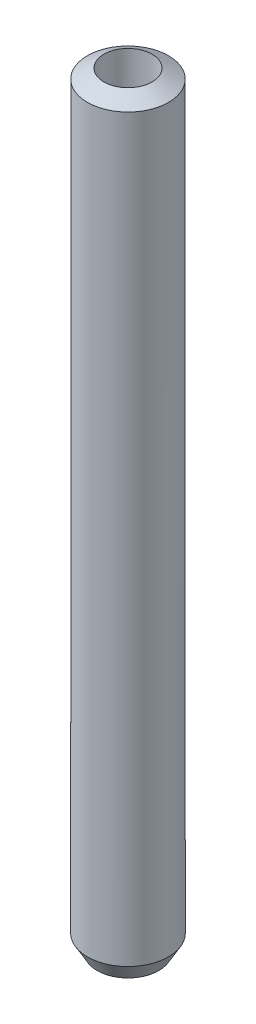
SolidWorks part; units mm, degrees
ref_plane "Front Plane" through (0, 0, 0) normal (0, 0, 1) x (1, 0, 0)
ref_plane "Top Plane" through (0, 0, 0) normal (0, 1, 0) x (1, 0, 0)
ref_plane "Right Plane" through (0, 0, 0) normal (1, 0, 0) x (0, 0, -1)
sketch "Sketch1" plane through (0, 0, 0) normal (0, 1, 0) x (1, 0, 0)
  circle A0 centre (0, 0) radius 7.5
  dimension "SHAFT_OD" = 15
extrude "Boss-Extrude1" add sketch "Sketch1" along normal blind 141.8844
sketch "Sketch2" plane through (0, 0, 0) normal (0, 1, 0) x (1, 0, 0)
  circle A0 centre (0, 0) radius 4.4596
  dimension "BORE_D" = 8.9192
extrude "Cut-Extrude1" cut sketch "Sketch2" along normal through all
chamfer "Chamfer1" distance 1.7909 angle 60 2 edges at (0, 141.8844, 7.5) (0, 0, 7.5) first distance on face at (0, 141.8844, 7.5) first distance on face at (0, 0, 4.4596)
